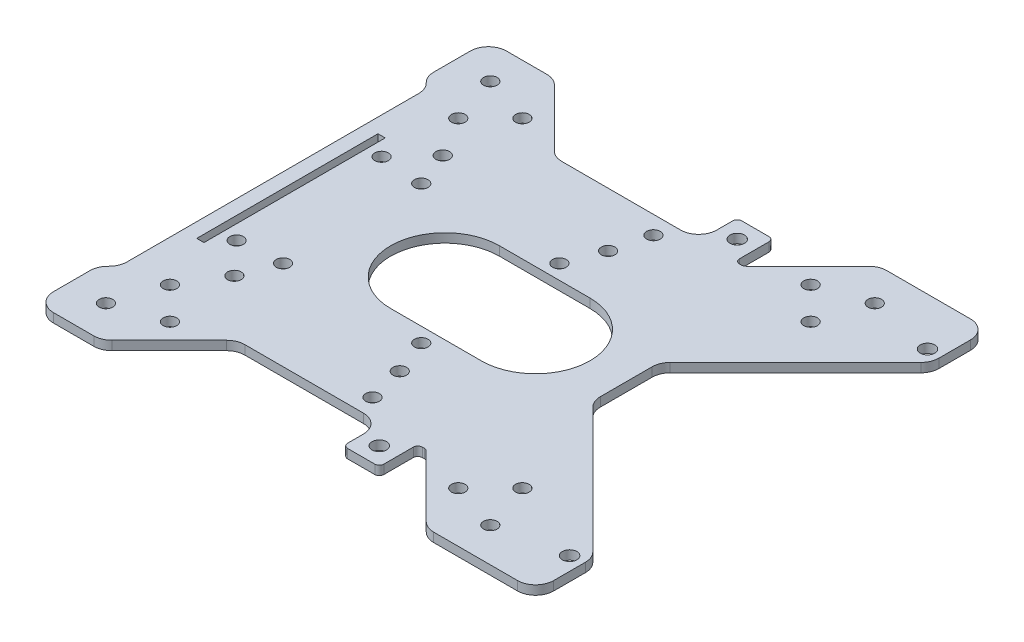
SolidWorks part; units mm, degrees
material "Thornel Mat VMA"
ref_plane "前视基准面" through (0, 0, 0) normal (0, 0, 1) x (1, 0, 0)
ref_plane "上视基准面" through (0, 0, 0) normal (0, 1, 0) x (1, 0, 0)
ref_plane "右视基准面" through (0, 0, 0) normal (1, 0, 0) x (0, 0, -1)
other "Configuration Table"
sketch "草图1" plane through (0, 0, 0) normal (0, 1, 0) x (1, 0, 0)
  line L1 (-60, -50) -> (60, -50)
  line L2 (-60, -50) -> (-60, 50)
  line L3 (-60, 50) -> (60, 50)
  line L4 (60, -50) -> (60, 50)
  line L5 (-60, -50) -> (60, 50) construction
  line L6 (-60, 50) -> (60, -50) construction
  point P0 (0, 0)
  dimension "D1" = 120
  dimension "D2" = 100
extrude "凸台-拉伸1" add sketch "草图1" along normal blind 2
sketch "草图2" plane through (0, 2, 0) normal (0, 1, 0) x (1, 0, 0)
  line L1 (15, 39.5) -> (57, 39.5) construction
  line L2 (15, 39.5) -> (15, -39.5) construction
  line L3 (15, -39.5) -> (57, -39.5) construction
  line L4 (57, 39.5) -> (57, -39.5) construction
  line L5 (-30.5, 15.25) -> (0, 15.25) construction
  line L6 (-30.5, 15.25) -> (-30.5, -15.25) construction
  line L7 (-30.5, -15.25) -> (0, -15.25) construction
  line L8 (0, 15.25) -> (0, -15.25) construction
  line L9 (-33.5, 23) -> (3, 23) construction
  line L10 (-33.5, 23) -> (-33.5, -23) construction
  line L11 (-33.5, -23) -> (3, -23) construction
  line L12 (3, 23) -> (3, -23) construction
  circle A0 centre (15, 39.5) radius 1.6
  circle A1 centre (57, 39.5) radius 1.6
  circle A2 centre (57, -39.5) radius 1.6
  circle A3 centre (15, -39.5) radius 1.6
  circle A4 centre (-30.5, 15.25) radius 1.5
  circle A5 centre (-30.5, -15.25) radius 1.5
  circle A6 centre (0, -15.25) radius 1.5
  circle A7 centre (0, 15.25) radius 1.5
  circle A8 centre (3, 23) radius 1.5
  circle A9 centre (-33.5, 23) radius 1.5
  circle A10 centre (-33.5, -23) radius 1.5
  circle A11 centre (3, -23) radius 1.5
  dimension "D4" = 3.2
  dimension "D5" = 3.2
  dimension "D6" = 3.2
  dimension "D7" = 3.2
  dimension "D11" = 3
  dimension "D12" = 3
  dimension "D13" = 3
  dimension "D14" = 3
  dimension "D19" = 3
  dimension "D20" = 3
  dimension "D21" = 3
  dimension "D22" = 3
  dimension "D1" = 79
  dimension "D2" = 42
  dimension "D3" = 39.5
  dimension "D8" = 30.5
  dimension "D9" = 30.5
  dimension "D10" = 15.25
  dimension "D15" = 36.5
  dimension "D16" = 46
  dimension "D17" = 23
  dimension "D18" = 3
  dimension "D23" = 3
  dimension "D24" = 15
extrude "切除-拉伸1" cut sketch "草图2" against normal through all
sketch "草图3" plane through (0, 2, 0) normal (0, 1, 0) x (1, 0, 0)
  line L0 (-1000, 0) -> (49000, 0) construction
  line L1 (-42.4264, 42.4264) -> (0, 0) construction
  line L2 (-42.9749, 27.7358) -> (35312.3642, 35383.0749) construction
  line L3 (0, -1000) -> (0, 49000) construction
  circle A0 centre (0, 0) radius 60 construction
  circle A1 centre (-42.4264, 42.4264) radius 1.5
  circle A2 centre (-31.8198, 38.8909) radius 1.5
  circle A3 centre (-38.8909, 31.8198) radius 1.5
  circle A4 centre (-31.8198, -38.8909) radius 1.5
  circle A5 centre (-38.8909, -31.8198) radius 1.5
  circle A6 centre (-42.4264, -42.4264) radius 1.5
  circle A7 centre (31.8198, 38.8909) radius 1.5
  circle A8 centre (38.8909, 31.8198) radius 1.5
  circle A9 centre (42.4264, 42.4264) radius 1.5
  circle A10 centre (31.8198, -38.8909) radius 1.5
  circle A11 centre (42.4264, -42.4264) radius 1.5
  circle A12 centre (38.8909, -31.8198) radius 1.5
  dimension "D1" = 120
  dimension "D3" = 3
  dimension "D6" = 3
  dimension "D7" = 3
  dimension "D8" = 5
  dimension "D9" = 5
  dimension "D2" = 45
  dimension "D4" = 90
  dimension "D5" = 10
extrude "切除-拉伸2" cut sketch "草图3" against normal through all
sketch "草图4" plane through (0, 2, 0) normal (0, 1, 0) x (1, 0, 0)
  line L0 (-60, 45.8579) -> (-48, 33.8579)
  line L1 (-60, 50) -> (-60, -50) construction
  line L2 (-48, 33.8579) -> (-48, -33.8579)
  line L3 (-48, -33.8579) -> (-60, -45.8579)
  line L4 (-60, -45.8579) -> (-60, 45.8579)
  line L7 (-35.8579, -50) -> (-20.8579, -35)
  line L8 (-60, -50) -> (60, -50) construction
  line L9 (-20.8579, -35) -> (11, -35)
  line L10 (11, -35) -> (11, -43.5)
  line L11 (11, -43.5) -> (19, -43.5)
  line L12 (19, -43.5) -> (19, -35)
  line L13 (19, -35) -> (20.8579, -35)
  line L14 (20.8579, -35) -> (35.8579, -50)
  line L15 (35.8579, -50) -> (-35.8579, -50)
  line L16 (-1000, 0) -> (49000, 0) construction
  line L17 (-74.5998, -85.9135) -> (-29.6985, -41.0122) construction
  line L18 (29.6985, -41.0122) -> (74.5998, -85.9135) construction
  line L19 (35.8579, 50) -> (-35.8579, 50)
  line L20 (-35.8579, 50) -> (-20.8579, 35)
  line L21 (-20.8579, 35) -> (11, 35)
  line L22 (11, 35) -> (11, 43.5)
  line L23 (11, 43.5) -> (19, 43.5)
  line L24 (19, 35) -> (20.8579, 35)
  line L25 (19, 43.5) -> (19, 35)
  line L26 (20.8579, 35) -> (35.8579, 50)
  line L36 (60, -37.3726) -> (30, -7.3726)
  line L37 (60, -50) -> (60, 50) construction
  line L38 (30, -7.3726) -> (30, 7.3726)
  line L39 (30, 7.3726) -> (60, 37.3726)
  line L40 (60, 37.3726) -> (60, -37.3726)
  line L42 (85.9135, -74.5998) -> (41.0122, -29.6985) construction
  line L43 (41.0122, 29.6985) -> (85.9135, 74.5998) construction
  line L44 (-41.0122, -29.6985) -> (-85.9135, -74.5998) construction
  line L45 (-85.9135, 74.5998) -> (-41.0122, 29.6985) construction
  circle A0 centre (15, -39.5) radius 1.6 construction
  point P4 (-114.1831, -36.3002)
  dimension "D7" = 4
  dimension "D2" = 2
  dimension "D3" = 30
  dimension "D5" = 12
  dimension "D6" = 45
  dimension "D8" = 2
  dimension "D9" = 2
  dimension "D10" = 4
  dimension "D11" = 4
  dimension "D12" = 15
  dimension "D13" = 15
  dimension "D15" = 8
  dimension "D16" = 2
  dimension "D17" = 8
extrude "切除-拉伸4" cut sketch "草图4" against normal through all
fillet "圆角1" radius 1 8 edges at (20.8579, 1, 35) (19, 1, 35) (19, 1, 43.5) (11, 1, 43.5) (20.8579, 1, -35) (19, 1, -35) (11, 1, -43.5) (19, 1, -43.5)
fillet "圆角2" radius 4 8 edges at (30, 1, 7.3726) (30, 1, -7.3726) (-48, 1, -33.8579) (-48, 1, 33.8579) (-20.8579, 1, 35) (-20.8579, 1, -35) (11, 1, 35) (11, 1, -35)
sketch "草图6" plane through (0, 2, 0) normal (0, 1, 0) x (1, 0, 0)
  line L1 (-77.325, 60.8605) -> (-50.4264, 60.8605)
  line L2 (-77.325, 60.8605) -> (-77.325, -64.9243)
  line L3 (-77.325, -64.9243) -> (-50.4264, -64.9243)
  line L4 (-50.4264, 60.8605) -> (-50.4264, -64.9243)
  circle A0 centre (-42.4264, 42.4264) radius 1.5 construction
  dimension "D1" = 8
extrude "切除-拉伸5" cut sketch "草图6" against normal through all
fillet "圆角3" radius 4 12 edges at (-35.8579, 1, 50) (-50.4264, 1, 36.2843) (-50.4264, 1, 50) (35.8579, 1, 50) (60, 1, 50) (60, 1, 37.3726) (60, 1, -37.3726) (60, 1, -50) (35.8579, 1, -50) (-35.8579, 1, -50) (-50.4264, 1, -36.2843) (-50.4264, 1, -50)
sketch "草图7" plane through (0, 2, 0) normal (0, 1, 0) x (1, 0, 0)
  line L0 (-10, 0) -> (10, 0) construction
  line L3 (-10, 12) -> (10, 12)
  line L4 (-10, -12) -> (10, -12)
  arc A3 (-10, 12) -> (-10, -12) centre (-10, 0) ccw
  arc A4 (10, -12) -> (10, 12) centre (10, 0) ccw
  point P2 (0, 0)
  dimension "D1" = 20
  dimension "D2" = 12
extrude "切除-拉伸6" cut sketch "草图7" against normal through all
sketch "草图8" plane through (0, 2, 0) normal (0, 1, 0) x (1, 0, 0)
  line L0 (-48, -32.201) -> (-48, 32.201) construction
  line L1 (-43.2, -20) -> (-44.8, -20)
  line L2 (-43.2, -20) -> (-43.2, 20)
  line L3 (-43.2, 20) -> (-44.8, 20)
  line L4 (-44.8, -20) -> (-44.8, 20)
  line L5 (-43.2, -20) -> (-44.8, 20) construction
  line L6 (-43.2, 20) -> (-44.8, -20) construction
  point P0 (-44, 0)
  dimension "D1" = 1.6
  dimension "D2" = 4
  dimension "D3" = 40
extrude "切除-拉伸7" cut sketch "草图8" against normal through all
sketch "草图9" plane through (0, 2, 0) normal (0, 1, 0) x (1, 0, 0)
  line L1 (-1000, 0) -> (49000, 0) construction
  circle A0 centre (-40, 16) radius 1.5
  circle A2 centre (5, 31) radius 1.5
  circle A4 centre (5, -31) radius 1.5
  circle A5 centre (-40, -16) radius 1.5
  dimension "D1" = 3
  dimension "D2" = 31
  dimension "D3" = 3
  dimension "D4" = 40
  dimension "D5" = 16
  dimension "D6" = 5
extrude "切除-拉伸8" cut sketch "草图9" against normal through all
